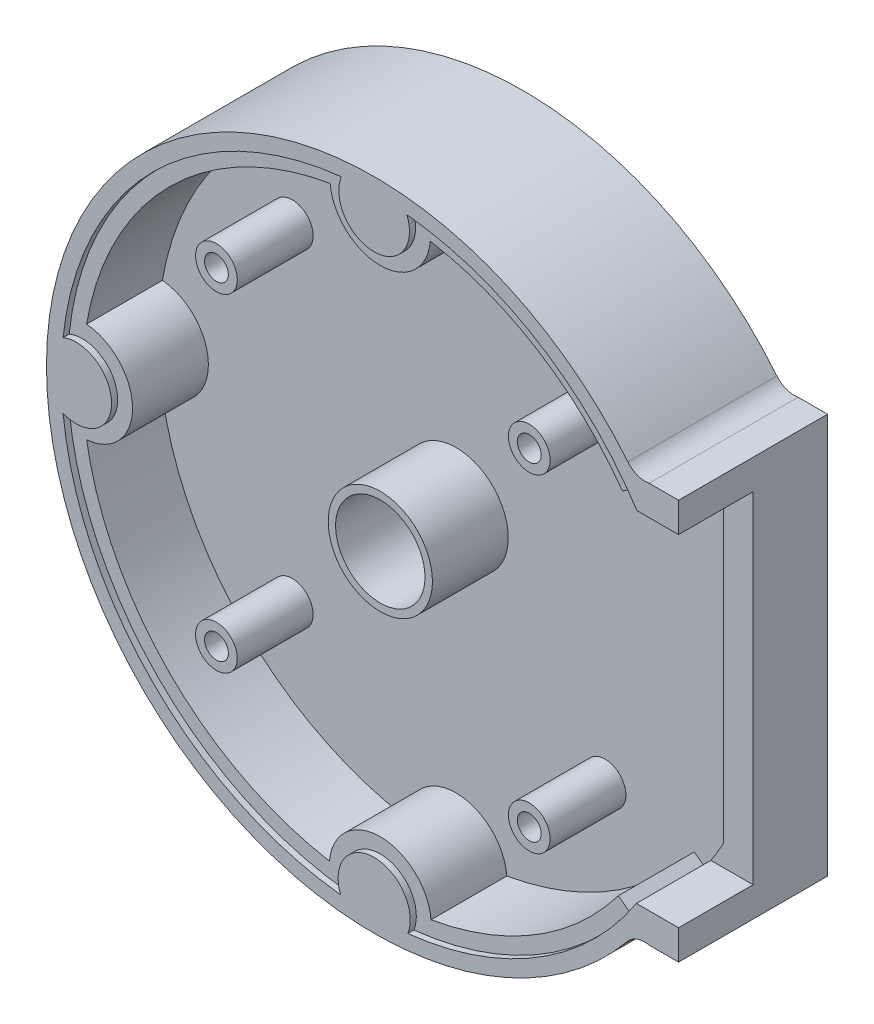
SolidWorks part; units mm, degrees
ref_plane "Front Plane" through (0, 0, 0) normal (0, 0, 1) x (1, 0, 0)
ref_plane "Top Plane" through (0, 0, 0) normal (0, 1, 0) x (1, 0, 0)
ref_plane "Right Plane" through (0, 0, 0) normal (1, 0, 0) x (0, 0, -1)
sketch "Sketch2" plane through (0, 0, 0) normal (0, 0, 1) x (1, 0, 0)
  circle A0 centre (0, 0) radius 22
  dimension "D1" = 44
extrude "Boss-Extrude1" add sketch "Sketch2" along normal blind 10
sketch "Sketch3" plane through (0, 0, 10) normal (0, 0, 1) x (1, 0, 0)
  circle A0 centre (0, 0) radius 21
  dimension "D1" = 42
extrude "Cut-Extrude2" cut sketch "Sketch3" against normal blind 5.5
sketch "Sketch4" plane through (0, 0, 4.5) normal (0, 0, 1) x (1, 0, 0)
  line L0 (-11, -11.015) -> (10, -11.015) construction
  line L1 (-11, 11) -> (10, 11) construction
  line L2 (10, 11) -> (10, -11.015) construction
  line L3 (-11, 11) -> (0, 0) construction
  line L4 (0, 0) -> (10, -11.015) construction
  line L5 (10, 11) -> (0, 0) construction
  line L6 (0, 0) -> (-11, -11.015) construction
  line L8 (-11, 11) -> (-11, -11.015) construction
  circle A0 centre (-11, 11) radius 0.8
  circle A1 centre (10, 11) radius 0.8
  circle A2 centre (10, -11.015) radius 0.8
  circle A3 centre (-11, -11.015) radius 0.8
  circle A4 centre (-11, 11) radius 1.4
  circle A5 centre (10, 11) radius 1.4
  circle A6 centre (10, -11.015) radius 1.4
  circle A7 centre (-11, -11.015) radius 1.4
  dimension "D1" = 1.6
  dimension "D2" = 1.6
  dimension "D3" = 1.6
  dimension "D4" = 1.6
  dimension "D6" = 2.8
  dimension "D7" = 2.8
  dimension "D8" = 2.8
  dimension "D9" = 2.8
  dimension "D5" = 22.015
extrude "Boss-Extrude2" add sketch "Sketch4" along normal blind 5.09 contours A4 A0 | A5 A1 | A6 A2 | A7 A3
sketch "Sketch5" plane through (0, 0, 4.5) normal (0, 0, 1) x (1, 0, 0)
  circle A1 centre (0, 0) radius 3
extrude "Cut-Extrude3" cut sketch "Sketch5" against normal blind 13
sketch "Sketch6" plane through (0, 0, 4.5) normal (0, 0, 1) x (1, 0, 0)
  circle A0 centre (0, 0) radius 3.5
  dimension "D1" = 7
extrude "Boss-Extrude3" add sketch "Sketch6" along normal blind 5.09
sketch "Sketch18" plane through (0, 0, 9.59) normal (0, 0, 1) x (1, 0, 0)
  circle A0 centre (-11, 11) radius 0.8
  circle A1 centre (10, 11) radius 0.8
  circle A2 centre (10, -11.015) radius 0.8
  circle A3 centre (-11, -11.015) radius 0.8
extrude "Cut-Extrude7" cut sketch "Sketch18" against normal through all
sketch "Sketch20" plane through (0, 0, 10) normal (0, 0, 1) x (1, 0, 0)
  line L5 (17.3708, 11.4007) -> (27.4615, 11.4007)
  line L6 (17.3708, 11.4007) -> (17.3708, -11.4529)
  line L7 (17.3708, -11.4529) -> (27.4615, -11.4529)
  line L8 (27.4615, 11.4007) -> (27.4615, -11.4529)
extrude "Cut-Extrude8" cut sketch "Sketch20" against normal blind 5
sketch3d "3DSketch3" plane through (0, 0, 0) normal (0, 0, 1) x (1, 0, 0)
  dimension "D1" = 25
sketch "Sketch24" plane through (20.4592, 0, 0) normal (1, 0, 0) x (0, 0, -1)
  line L0 (-10, 11.4007) -> (-5, 11.4007) construction
  line L5 (-5, -11.4529) -> (-10, -11.4529) construction
  line L6 (-10, 11.4007) -> (-5, 11.4007)
  line L7 (-5, -11.4529) -> (-10, -11.4529)
  line L8 (-10, -11.4529) -> (-10, -13.4529)
  line L9 (-10, -13.4529) -> (0, -13.4529)
  line L10 (0, -13.4529) -> (0, 13.4007)
  line L11 (0, 13.4007) -> (-10, 13.4007)
  line L12 (-10, 13.4007) -> (-10, 11.4007)
  line L13 (-5, 11.4007) -> (-5, -11.4529)
  line L14 (0, -22) -> (0, 22) construction
  dimension "D1" = 2
  dimension "D2" = 2
extrude "Boss-Extrude12" add sketch "Sketch24" along normal blind 0.5 and the other way blind 2
fillet "Fillet3" radius 1.5 2 edges at (18.4592, -11.9691, 5) (18.4592, 11.9691, 5)
sketch "Sketch25" plane through (0, 0, 10) normal (0, 0, 1) x (1, 0, 0)
  line L1 (20.4337, 14.3279) -> (34.7, 14.3279)
  line L2 (20.4337, 14.3279) -> (20.4337, -14.1246)
  line L3 (20.4337, -14.1246) -> (34.7, -14.1246)
  line L4 (34.7, 14.3279) -> (34.7, -14.1246)
extrude "Cut-Extrude9" cut sketch "Sketch25" against normal up to next
sketch "Sketch30" plane through (0, 0, 4.5) normal (0, 0, 1) x (1, 0, 0)
  line L3 (17.3805, -11.3824) -> (17.8379, -11.3824)
  line L4 (18.4115, -10.8088) -> (18.4115, 10.7975)
  line L5 (17.8174, 11.3916) -> (17.3485, 11.3916)
  arc A2 (-2.2604, -20.878) -> (2.2555, -20.8785) centre (0, 0) ccw
  arc A3 (-20.8844, 2.2003) -> (-20.8839, -2.2053) centre (0, 0) ccw
  arc A4 (2.1977, 20.8847) -> (-2.203, 20.8841) centre (0, 0) ccw
  arc A21 (-20.7035, -2.4134) -> (-20.7075, -2.4644) centre (-20.5462, -2.4514) ccw
  arc A22 (-20.7075, -2.4644) -> (-2.5805, -20.6934) centre (-0.0012, -0.0012) ccw
  arc A23 (-2.5805, -20.6934) -> (-2.5025, -20.6774) centre (-2.5671, -20.5606) ccw
  arc A24 (-2.5025, -20.6774) -> (-2.3675, -20.5234) centre (-2.4925, -20.55) ccw
  arc A25 (2.3755, -20.4624) -> (-2.3675, -20.5234) centre (-0.0024, -20.0021) ccw
  arc A26 (2.3755, -20.4624) -> (2.3755, -20.5084) centre (2.5067, -20.4854) ccw
  arc A27 (2.3755, -20.5084) -> (2.5175, -20.6264) centre (2.5021, -20.5004) ccw
  arc A28 (2.5175, -20.6264) -> (17.3805, -11.3824) centre (-0.0038, -0.0018) ccw
  arc A29 (17.8379, -11.3824) -> (18.4115, -10.8088) centre (17.8379, -10.8088) ccw
  arc A30 (18.4115, 10.7975) -> (17.8174, 11.3916) centre (17.8174, 10.7975) ccw
  arc A31 (17.3485, 11.3916) -> (2.5072, 20.6037) centre (-0.0023, -0.0005) ccw
  arc A32 (2.5072, 20.6037) -> (2.3675, 20.5006) centre (2.4919, 20.4781) ccw
  arc A33 (2.3675, 20.5006) -> (2.3365, 20.3946) centre (2.4598, 20.4161) ccw
  arc A34 (-2.3425, 20.3886) -> (2.3365, 20.3946) centre (-0.0025, 19.9971) ccw
  arc A35 (-2.3425, 20.3886) -> (-2.4615, 20.5366) centre (-2.4684, 20.4093) ccw
  arc A36 (-2.4615, 20.5366) -> (-2.5115, 20.5406) centre (-2.4948, 20.4353) ccw
  arc A37 (-2.5115, 20.5406) -> (-20.5455, 2.5026) centre (-0.0029, -0.0015) ccw
  arc A38 (-20.5455, 2.5026) -> (-20.5425, 2.4546) centre (-20.4297, 2.4858) ccw
  arc A39 (-20.5425, 2.4546) -> (-20.3945, 2.3376) centre (-20.4152, 2.4637) ccw
  arc A40 (-20.5485, -2.3114) -> (-20.3945, 2.3376) centre (-20.0028, -0.0024) ccw
  arc A41 (-20.5485, -2.3114) -> (-20.7035, -2.4134) centre (-20.5768, -2.4372) ccw
  arc A42 (-20.7035, -2.4134) -> (-20.7075, -2.4644) centre (-20.5462, -2.4514) ccw
  arc A44 (-2.5805, -20.6934) -> (-2.5025, -20.6774) centre (-2.5671, -20.5606) ccw
  arc A45 (-2.5025, -20.6774) -> (-2.3675, -20.5234) centre (-2.4925, -20.55) ccw
  arc A46 (2.2555, -20.8785) -> (-2.2604, -20.878) centre (-0.0024, -20.0021) ccw
  arc A47 (2.3755, -20.4624) -> (2.3755, -20.5084) centre (2.5067, -20.4854) ccw
  arc A48 (2.3755, -20.5084) -> (2.5175, -20.6264) centre (2.5021, -20.5004) ccw
  arc A54 (2.3364, 20.3951) -> (2.3365, 20.3946) centre (2.4598, 20.4161) ccw
  arc A55 (-2.203, 20.8841) -> (2.1977, 20.8847) centre (-0.0025, 19.9971) ccw
  arc A56 (-2.3425, 20.3886) -> (-2.4615, 20.5366) centre (-2.4684, 20.4093) ccw
  arc A57 (-2.4615, 20.5366) -> (-2.5115, 20.5406) centre (-2.4948, 20.4353) ccw
  arc A59 (-20.5455, 2.5026) -> (-20.5425, 2.4546) centre (-20.4297, 2.4858) ccw
  arc A60 (-20.5425, 2.4546) -> (-20.3945, 2.3376) centre (-20.4152, 2.4637) ccw
  arc A61 (-20.8839, -2.2053) -> (-20.8844, 2.2003) centre (-20.0028, -0.0024) ccw
  arc A62 (-20.5485, -2.3114) -> (-20.7035, -2.4134) centre (-20.5768, -2.4372) ccw
  arc M30 (18.4592, 10.013) -> (18.4592, -10.013) centre (0, 0) ccw
  dimension "D1" = 0
extrude "Boss-Extrude14" add sketch "Sketch30" along normal up to surface (5.5 mm away) contours A46 M30 | A54 A55 M30 | A61 M30
sketch "Sketch33" plane through (0, 0, 4.5) normal (0, 0, 1) x (1, 0, 0)
  line L1 (3.3583, 19.716) -> (3.3583, 19.716)
  line L2 (18.4592, -10.013) -> (18.4592, 10.013)
  line L3 (2.3364, 20.3951) -> (2.3365, 20.3946)
  line L5 (2.3364, 20.3951) -> (2.3365, 20.3946)
  line L6 (16.2631, 11.641) -> (17.0762, 12.223)
  line L7 (15.9849, -12.0201) -> (16.7842, -12.6211)
  line L9 (17.4592, -9.7559) -> (17.4592, 9.7559) construction
  line L10 (18.4592, -10.013) -> (18.4592, 10.013) construction
  arc A0 (-3.3633, 19.7152) -> (-19.7161, 3.358) centre (0, 0) ccw
  arc A1 (-19.7153, -3.3627) -> (-19.7161, 3.358) centre (-20.0028, -0.0024) ccw
  arc A2 (-19.7153, -3.3627) -> (-3.4115, -19.7069) centre (0, 0) ccw
  arc A3 (3.4069, -19.7077) -> (-3.4115, -19.7069) centre (-0.0024, -20.0021) ccw
  arc A4 (3.4069, -19.7077) -> (15.9849, -12.0201) centre (0, 0) ccw
  arc A5 (16.2631, 11.641) -> (3.3583, 19.716) centre (0, 0) ccw
  arc A6 (3.3583, 19.716) -> (3.3583, 19.716) centre (3.3583, 19.716) cw
  arc A7 (-3.3633, 19.7152) -> (3.3583, 19.716) centre (-0.0025, 19.9971) ccw
  arc A8 (-2.203, 20.8841) -> (-20.8844, 2.2003) centre (0, 0) ccw
  arc A9 (-20.8839, -2.2053) -> (-20.8844, 2.2003) centre (-20.0028, -0.0024) ccw
  arc A10 (-20.8839, -2.2053) -> (-2.2604, -20.878) centre (0, 0) ccw
  arc A11 (2.2555, -20.8785) -> (-2.2604, -20.878) centre (-0.0024, -20.0021) ccw
  arc A12 (2.2555, -20.8785) -> (18.4592, -10.013) centre (0, 0) ccw
  arc A13 (18.4592, 10.013) -> (2.1977, 20.8847) centre (0, 0) ccw
  arc A14 (2.3364, 20.3951) -> (2.1977, 20.8847) centre (-0.0025, 19.9971) ccw
  arc A15 (-2.203, 20.8841) -> (2.3365, 20.3946) centre (-0.0025, 19.9971) ccw
  arc A16 (-2.203, 20.8841) -> (-20.8844, 2.2003) centre (0, 0) ccw
  arc A17 (-20.8839, -2.2053) -> (-20.8844, 2.2003) centre (-20.0028, -0.0024) ccw
  arc A18 (-20.8839, -2.2053) -> (-2.2604, -20.878) centre (0, 0) ccw
  arc A19 (2.2555, -20.8785) -> (-2.2604, -20.878) centre (-0.0024, -20.0021) ccw
  arc A20 (2.2555, -20.8785) -> (16.7842, -12.6211) centre (0, 0) ccw
  arc A21 (17.0762, 12.223) -> (2.1977, 20.8847) centre (0, 0) ccw
  arc A22 (2.3364, 20.3951) -> (2.1977, 20.8847) centre (-0.0025, 19.9971) ccw
  arc A23 (-2.203, 20.8841) -> (2.3365, 20.3946) centre (-0.0025, 19.9971) ccw
  arc A24 (3.4069, -19.7077) -> (17.4592, -9.7559) centre (0, 0) ccw construction
  arc A25 (2.2555, -20.8785) -> (18.4592, -10.013) centre (0, 0) ccw construction
  arc A26 (17.4592, 9.7559) -> (3.3583, 19.716) centre (0, 0) ccw construction
  arc A27 (18.4592, 10.013) -> (2.1977, 20.8847) centre (0, 0) ccw construction
  dimension "D1" = 0
  dimension "D2" = 1
extrude "Boss-Extrude15" add sketch "Sketch33" along normal blind 5.09
sketch "Sketch36" plane through (0, 0, 0) normal (0, 0, -1) x (-1, 0, 0)
  line L1 (-7.7483, 11) -> (-8.8742, 12.95)
  line L2 (-8.8742, 12.95) -> (-11.1258, 12.95)
  line L3 (-11.1258, 12.95) -> (-12.2517, 11)
  line L4 (-12.2517, 11) -> (-11.1258, 9.05)
  line L5 (-11.1258, 9.05) -> (-8.8742, 9.05)
  line L6 (-8.8742, 9.05) -> (-7.7483, 11)
  line L7 (12.5146, 12.6661) -> (10.3145, 13.1448)
  line L8 (10.3145, 13.1448) -> (8.7998, 11.4787)
  line L9 (8.7998, 11.4787) -> (9.4854, 9.3339)
  line L10 (9.4854, 9.3339) -> (11.6855, 8.8552)
  line L11 (11.6855, 8.8552) -> (13.2002, 10.5213)
  line L12 (13.2002, 10.5213) -> (12.5146, 12.6661)
  line L13 (13.1226, -10.2636) -> (11.4106, -8.8011)
  line L14 (11.4106, -8.8011) -> (9.288, -9.5525)
  line L15 (9.288, -9.5525) -> (8.8774, -11.7664)
  line L16 (8.8774, -11.7664) -> (10.5894, -13.2289)
  line L17 (10.5894, -13.2289) -> (12.712, -12.4776)
  line L18 (12.712, -12.4776) -> (13.1226, -10.2636)
  line L19 (-8.4923, -9.3427) -> (-10.6945, -8.8731)
  line L20 (-10.6945, -8.8731) -> (-12.2022, -10.5455)
  line L21 (-12.2022, -10.5455) -> (-11.5077, -12.6874)
  line L22 (-11.5077, -12.6874) -> (-9.3055, -13.1569)
  line L23 (-9.3055, -13.1569) -> (-7.7978, -11.4845)
  line L24 (-7.7978, -11.4845) -> (-8.4923, -9.3427)
  circle A0 centre (-10, 11) radius 0.8 construction
  circle A1 centre (-10, 11) radius 0.8
  circle A2 centre (-10, 11) radius 1.95 construction
  circle A3 centre (-10, -11.015) radius 0.8 construction
  circle A4 centre (11, -11.015) radius 0.8 construction
  circle A5 centre (11, 11) radius 0.8 construction
  circle A6 centre (-10, -11.015) radius 0.8
  circle A7 centre (11, -11.015) radius 0.8
  circle A8 centre (11, 11) radius 0.8
  circle A9 centre (11, 11) radius 1.95 construction
  circle A10 centre (11, -11.015) radius 1.95 construction
  circle A11 centre (-10, -11.015) radius 1.95 construction
  point P19 (12.9173, -11.3706)
  dimension "D1" = 3.9
  dimension "D2" = 3.9
  dimension "D3" = 3.9
  dimension "D4" = 3.9
extrude "Cut-Extrude10" cut sketch "Sketch36" against normal blind 2.5
